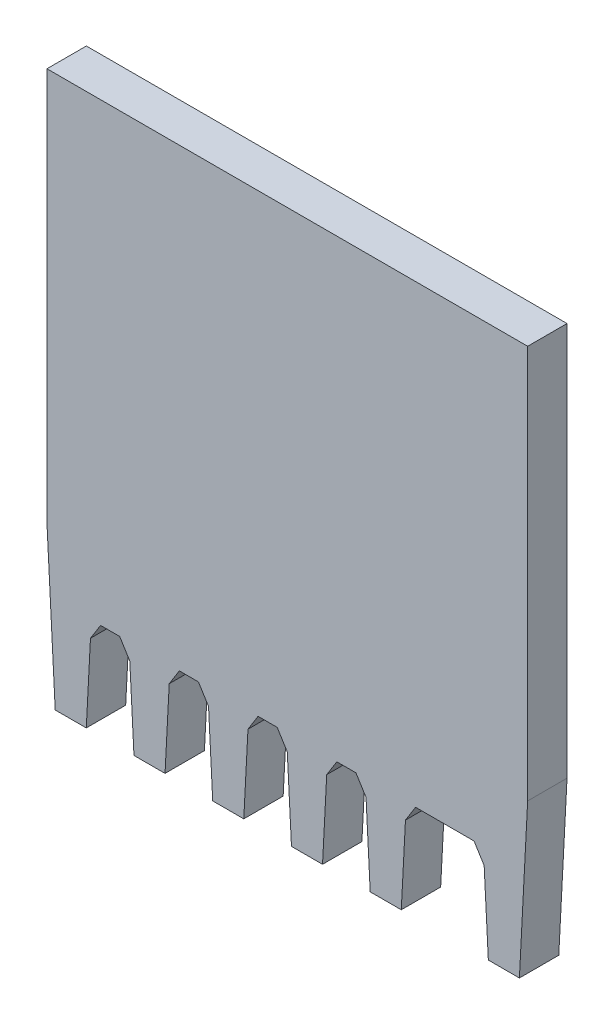
SolidWorks part; units mm, degrees
ref_plane "Front Plane" through (0, 0, 0) normal (0, 0, 1) x (1, 0, 0)
ref_plane "Top Plane" through (0, 0, 0) normal (0, 1, 0) x (1, 0, 0)
ref_plane "Right Plane" through (0, 0, 0) normal (1, 0, 0) x (0, 0, -1)
sketch "Sketch1" plane through (0, 0, 0) normal (0, 0, 1) x (1, 0, 0)
  line L0 (0, 0) -> (0, 21) construction
  line L1 (0, 21) -> (18.3124, 21) construction
  line L2 (18.3124, 21) -> (18.3124, 0) construction
  line L3 (18.3124, 0) -> (0, 0) construction
  line L4 (0, 3) -> (18.3124, 3) construction
  line L5 (0, 6) -> (18.3124, 6) construction
  line L6 (0.9062, 6) -> (0.9062, 0) construction
  line L7 (3.9062, 6) -> (3.9062, 0) construction
  line L8 (6.9062, 6) -> (6.9062, 0) construction
  line L9 (9.9062, 6) -> (9.9062, 0) construction
  line L10 (12.9062, 6) -> (12.9062, 0) construction
  line L11 (17.4062, 6) -> (17.4062, 0) construction
  line L12 (0.9062, 3) -> (3.9062, 3) construction
  line L13 (3.9062, 3) -> (6.9062, 3) construction
  line L14 (6.9062, 3) -> (9.9062, 3) construction
  line L15 (9.9062, 3) -> (12.9062, 3) construction
  line L16 (12.9062, 3) -> (17.4062, 3) construction
  line L17 (0.9062, 3) -> (0, 3) construction
  line L18 (17.4062, 3) -> (18.3124, 3) construction
  line L19 (2.4062, 3) -> (2.4062, 0) construction
  line L20 (5.4062, 3) -> (5.4062, 0) construction
  line L21 (8.4062, 3) -> (8.4062, 0) construction
  line L22 (11.4062, 3) -> (11.4062, 0) construction
  line L23 (15.1562, 3) -> (15.1562, 0) construction
  line L24 (14.4062, 3.75) -> (15.9062, 3.75) construction
  line L25 (0, 6) -> (0.3144, 0)
  line L26 (0.3144, 0) -> (1.4979, 0)
  line L27 (1.4979, 0) -> (1.6572, 3.0393)
  line L28 (3.1552, 3.0393) -> (3.3144, 0)
  line L29 (3.3144, 0) -> (4.4979, 0)
  line L30 (4.4979, 0) -> (4.6572, 3.0393)
  line L31 (6.1552, 3.0393) -> (6.3144, 0)
  line L32 (6.3144, 0) -> (7.4979, 0)
  line L33 (7.4979, 0) -> (7.6572, 3.0393)
  line L34 (9.1552, 3.0393) -> (9.3144, 0)
  line L35 (9.3144, 0) -> (10.4979, 0)
  line L36 (10.4979, 0) -> (10.6572, 3.0393)
  line L37 (12.1552, 3.0393) -> (12.3144, 0)
  line L38 (12.3144, 0) -> (13.4979, 0)
  line L39 (13.4979, 0) -> (13.6572, 3.0393)
  line L40 (16.6552, 3.0393) -> (16.8144, 0)
  line L41 (16.8144, 0) -> (17.9979, 0)
  line L42 (17.9979, 0) -> (18.3124, 6)
  line L44 (1.6572, 3.0393) -> (2.0426, 3.656)
  line L45 (0, 6) -> (0, 21)
  line L46 (0, 21) -> (18.3124, 21)
  line L47 (18.3124, 21) -> (18.3124, 6)
  line L48 (9.1562, 21) -> (9.1562, 6) construction
  line L49 (2.0426, 3.656) -> (2.7698, 3.656)
  line L50 (2.7698, 3.656) -> (3.1552, 3.0393)
  line L51 (4.6572, 3.0393) -> (5.0426, 3.656)
  line L52 (5.0426, 3.656) -> (5.7698, 3.656)
  line L53 (5.7698, 3.656) -> (6.1552, 3.0393)
  line L54 (7.6572, 3.0393) -> (8.0426, 3.656)
  line L55 (8.0426, 3.656) -> (8.7698, 3.656)
  line L56 (8.7698, 3.656) -> (9.1552, 3.0393)
  line L57 (10.6572, 3.0393) -> (11.0426, 3.656)
  line L58 (11.0426, 3.656) -> (11.7698, 3.656)
  line L59 (11.7698, 3.656) -> (12.1552, 3.0393)
  line L60 (13.6572, 3.0393) -> (14.0426, 3.656)
  line L61 (14.0426, 3.656) -> (16.2698, 3.656)
  line L62 (16.2698, 3.656) -> (16.6552, 3.0393)
  arc A0 (3.1552, 3.0393) -> (1.6572, 3.0393) centre (2.4062, 3) ccw construction
  arc A1 (6.1552, 3.0393) -> (4.6572, 3.0393) centre (5.4062, 3) ccw construction
  arc A2 (9.1552, 3.0393) -> (7.6572, 3.0393) centre (8.4062, 3) ccw construction
  arc A3 (12.1552, 3.0393) -> (10.6572, 3.0393) centre (11.4062, 3) ccw construction
  arc A4 (13.6572, 3.0393) -> (14.4062, 3.75) centre (14.4062, 3) cw construction
  arc A5 (16.6552, 3.0393) -> (15.9062, 3.75) centre (15.9062, 3) ccw construction
  dimension "D7" = 0.75
  dimension "D1" = 3
  dimension "D2" = 6
  dimension "D3" = 15
  dimension "D4" = 3
  dimension "D6" = 4.5
  dimension "D8" = 3
  dimension "D9" = 18.3124
  dimension "D10" = 21
extrude "Boss-Extrude1" add sketch "Sketch1" along normal blind 1.5
sketch "Sketch3" plane through (0, 0, 0) normal (0, 0, 1) x (1, 0, 0)
  line L0 (-0.4005, 6) -> (18.7129, 6)
  line L1 (18.7129, 3) -> (-0.4005, 3) construction
  line L2 (-0.4005, 0) -> (18.7129, 0) construction
  line L3 (-0.4005, -0.5) -> (18.7129, -0.5) construction
  line L4 (18.7129, -0.5) -> (18.7129, 6) construction
  line L5 (-0.4005, 6) -> (-0.4005, -0.5) construction
  line L6 (18.3124, 0) -> (0, 0) construction
  line L7 (0, 3) -> (18.3124, 3) construction
  line L8 (0, 6) -> (18.3124, 6) construction
  line L9 (0.3407, -0.5) -> (0, 6) construction
  line L10 (18.3124, 6) -> (17.9717, -0.5) construction
  line L11 (17.9979, 0) -> (18.3124, 6) construction
  line L12 (0, 6) -> (0.3144, 0) construction
  line L13 (5.4062, 6) -> (5.4062, -0.5) construction
  line L14 (3.9062, 6) -> (3.9062, -0.5) construction
  line L15 (5.4062, 3) -> (5.4062, 0) construction
  line L16 (3.1572, 3) -> (3.3407, -0.5) construction
  line L17 (2.7567, 3) -> (2.9401, -0.5)
  line L18 (3.1552, 3.0393) -> (3.3144, 0) construction
  line L19 (2.9401, -0.5) -> (4.8723, -0.5)
  line L20 (4.8723, -0.5) -> (5.0557, 3)
  line L21 (2.8484, 1.25) -> (3.2478, 1.2709) construction
  line L22 (5.9401, -0.5) -> (5.7567, 3)
  line L26 (7.8723, -0.5) -> (5.9401, -0.5)
  line L27 (8.0557, 3) -> (7.8723, -0.5)
  line L30 (2.4062, -0.5) -> (2.4062, 6) construction
  line L31 (2.4062, 3) -> (2.4062, 0) construction
  line L32 (8.4062, 6) -> (8.4062, -0.5) construction
  line L34 (11.4062, -0.5) -> (11.4062, 6) construction
  line L35 (15.1562, -0.5) -> (15.1562, 6) construction
  line L36 (8.4062, 3) -> (8.4062, 0) construction
  line L37 (11.4062, 3) -> (11.4062, 0) construction
  line L38 (15.1562, 3) -> (15.1562, 0) construction
  line L39 (10.8723, -0.5) -> (11.0557, 3)
  line L40 (8.9401, -0.5) -> (10.8723, -0.5)
  line L41 (8.7567, 3) -> (8.9401, -0.5)
  line L42 (11.9401, -0.5) -> (11.7567, 3)
  line L43 (13.8723, -0.5) -> (11.9401, -0.5)
  line L44 (14.0557, 3) -> (13.8723, -0.5)
  line L45 (16.4401, -0.5) -> (18.3723, -0.5)
  line L46 (16.2567, 3) -> (16.4401, -0.5)
  line L47 (18.3723, -0.5) -> (18.7129, 6)
  line L48 (1.8723, -0.5) -> (-0.0599, -0.5)
  line L49 (2.0557, 3) -> (1.8723, -0.5)
  line L50 (-0.0599, -0.5) -> (-0.4005, 6)
  line L51 (16.2567, 3) -> (14.0557, 3)
  line L52 (11.7567, 3) -> (11.0557, 3)
  line L53 (8.7567, 3) -> (8.0557, 3)
  line L54 (5.7567, 3) -> (5.0557, 3)
  line L55 (2.7567, 3) -> (2.0557, 3)
  dimension "D1" = 0.5
  dimension "D2" = 0.4
ref_plane "Plane1" through (3.9062, 0, 0) normal (1, 0, 0) x (0, 0, -1)
sketch "Sketch4" plane through (3.9062, 0, 0) normal (1, 0, 0) x (0, 0, -1)
  line L0 (0, 6) -> (0, -0.5) construction
  line L1 (0.6, 6) -> (-2.1, 6) construction
  line L2 (0.6, 6) -> (0.6, -0.5) construction
  line L3 (0.6, -0.5) -> (-2.1, -0.5) construction
  line L4 (-2.1, 6) -> (-2.1, -0.5) construction
  line L5 (-0.75, -0.5) -> (-0.75, 6) construction
  line L6 (-1.5, 6) -> (-1.5, -0.5) construction
  line L7 (0.6, 2.4005) -> (-2.1, 2.4005) construction
  line L8 (0.3, 6) -> (0.3, -0.5) construction
  line L9 (0.6, 2.4005) -> (3.846, 6) construction
  line L10 (2.2302, 6) -> (0.6, 4.1923) construction
  line L11 (0.6, 4.1923) -> (1.7139, 3.1878) construction
  line L12 (1.7139, 3.1878) -> (4.25, 6)
  line L13 (4.25, 6) -> (0.6, 6) construction
  line L14 (0.3, 1) -> (-1.8, 1) construction
  line L15 (-2.1, 0) -> (0.6, 0) construction
  line L16 (1.7139, 3.1878) -> (1.4912, 3.3887)
  line L17 (1.4912, 3.3887) -> (0.6, 2.4005)
  line L18 (-3.2139, 3.1878) -> (-5.75, 6)
  line L19 (-3.2139, 3.1878) -> (-2.9912, 3.3887)
  line L20 (-2.9912, 3.3887) -> (-2.1, 2.4005)
  line L21 (-2.1, 6) -> (-5.75, 6) construction
  line L22 (0.6, 3.0724) -> (3.2401, 6) construction
  arc A0 (0.4965, 2.2224) -> (0.6, -0.5) centre (4.2, 1) ccw
  arc A1 (0.6, 2.4005) -> (0.4965, 2.2224) centre (0.9713, 2.0656) ccw
  arc A2 (-2.1, 2.4005) -> (-1.9965, 2.2224) centre (-2.4713, 2.0656) cw
  arc A3 (-1.9965, 2.2224) -> (-2.1, -0.5) centre (-5.7, 1) cw
  dimension "D6" = 0.5
  dimension "D1" = 0.6
  dimension "D2" = 0.3
  dimension "D3" = 1.5
  dimension "D4" = 1
  dimension "D5" = 0.3
  dimension "D7" = 10
sketch "Sketch5" plane through (0, 0, 0) normal (1, 0, 0) x (0, 0, -1)
  line L0 (2.2302, 6) -> (0.6, 4.1923) construction
  line L1 (0.6, 4.1923) -> (1.7139, 3.1878) construction
  line L2 (1.7139, 3.1878) -> (4.25, 6) construction
  line L3 (2.2302, 6) -> (0.6, 4.1923) construction
  line L4 (0.6, 4.1923) -> (1.7139, 3.1878) construction
  line L5 (1.7139, 3.1878) -> (4.25, 6) construction
ref_plane "Plane2" through (0, 2.6105, -2.3541) normal (0, 0.7426, -0.6697) x (1, 0, 0)
sketch "Sketch6" plane through (0, 2.6105, -2.3541) normal (0, 0.7426, -0.6697) x (1, 0, 0)
  line L1 (3.9062, -2.362) -> (3.9062, -0.862) construction
  line L2 (3.9062, -2.362) -> (3.9062, -5.0612) construction
  line L3 (4.6562, -5.0612) -> (3.1562, -5.0612)
  line L4 (4.6562, -1.612) -> (3.1562, -1.612) construction
  line L5 (3.1562, -1.612) -> (3.1562, -5.0612)
  line L6 (4.6562, -1.612) -> (4.6562, -5.0612)
  line L10 (2.4062, -5.0612) -> (15.1562, -5.0612) construction
  line L11 (15.1562, -5.0612) -> (15.1562, -0.862) construction
  line L12 (15.1562, -0.862) -> (2.4062, -0.862) construction
  line L13 (2.4062, -0.862) -> (2.4062, -5.0612) construction
  line L14 (15.1562, 0.3349) -> (15.1562, -4.0182) construction
  line L15 (2.4062, 0.3349) -> (2.4062, -4.0182) construction
  line L16 (11.4062, -5.0612) -> (11.4062, -0.862) construction
  line L17 (8.4062, -5.0612) -> (8.4062, -0.862) construction
  line L18 (5.4062, -5.0612) -> (5.4062, -0.862) construction
  line L19 (5.4062, -4.0182) -> (5.4062, 0.3349) construction
  line L20 (8.4062, -4.0182) -> (8.4062, 0.3349) construction
  line L21 (11.4062, 0.3349) -> (11.4062, -4.0182) construction
  line L22 (0.1562, -1.612) -> (0.1562, -5.0612)
  line L23 (0.1562, -5.0612) -> (1.6562, -5.0612)
  line L24 (1.6562, -1.612) -> (1.6562, -5.0612)
  line L25 (7.6562, -1.612) -> (7.6562, -5.0612)
  line L26 (6.1562, -5.0612) -> (7.6562, -5.0612)
  line L27 (6.1562, -1.612) -> (6.1562, -5.0612)
  line L28 (10.6562, -1.612) -> (10.6562, -5.0612)
  line L29 (10.6562, -5.0612) -> (9.1562, -5.0612)
  line L30 (9.1562, -1.612) -> (9.1562, -5.0612)
  line L31 (13.6562, -1.612) -> (13.6562, -5.0612)
  line L32 (12.1562, -5.0612) -> (13.6562, -5.0612)
  line L33 (12.1562, -1.612) -> (12.1562, -5.0612)
  line L34 (18.1562, -1.612) -> (18.1562, -5.0612)
  line L35 (18.1562, -5.0612) -> (16.6562, -5.0612)
  line L36 (16.6562, -1.612) -> (16.6562, -5.0612)
  circle A0 centre (3.9062, -1.612) radius 0.75 construction
  arc A1 (4.6562, -1.612) -> (3.1562, -1.612) centre (3.9062, -1.612) ccw
  arc A2 (0.1562, -1.612) -> (1.6562, -1.612) centre (0.9062, -1.612) cw
  arc A3 (6.1562, -1.612) -> (7.6562, -1.612) centre (6.9062, -1.612) cw
  arc A4 (10.6562, -1.612) -> (9.1562, -1.612) centre (9.9062, -1.612) ccw
  arc A5 (12.1562, -1.612) -> (13.6562, -1.612) centre (12.9062, -1.612) cw
  arc A6 (18.1562, -1.612) -> (16.6562, -1.612) centre (17.4062, -1.612) ccw
ref_plane "Plane3" through (0, 1.6223, -1.463) normal (0, 0.7426, -0.6697) x (1, 0, 0)
sketch "Sketch7" plane through (0, 1.6223, -1.463) normal (0, 0.7426, -0.6697) x (1, 0, 0)
  line L0 (3.1562, -1.612) -> (3.1562, -5.0612) construction
  line L1 (4.6562, -5.0612) -> (3.1562, -5.0612) construction
  line L2 (4.6562, -1.612) -> (4.6562, -5.0612) construction
  line L3 (3.1562, -1.612) -> (3.1562, -5.0612) construction
  line L4 (4.6562, -5.0612) -> (3.1562, -5.0612) construction
  line L5 (4.6562, -1.612) -> (4.6562, -5.0612) construction
  line L6 (3.9062, -0.862) -> (3.9062, -5.0612) construction
  line L7 (4.6562, -1.612) -> (3.1562, -1.612) construction
  line L8 (4.6562, -2.362) -> (3.1562, -2.362) construction
  line L9 (3.4562, -1.612) -> (3.4562, -2.362)
  line L10 (3.4562, -2.362) -> (4.3562, -2.362)
  line L11 (4.3562, -2.362) -> (4.3562, -1.612)
  line L12 (2.4062, -0.862) -> (2.4062, -5.0612) construction
  line L13 (2.4062, -5.0612) -> (15.1562, -5.0612) construction
  line L14 (15.1562, -0.862) -> (2.4062, -0.862) construction
  line L15 (5.4062, -5.0612) -> (5.4062, -0.862) construction
  line L16 (8.4062, -5.0612) -> (8.4062, -0.862) construction
  line L17 (11.4062, -5.0612) -> (11.4062, -0.862) construction
  line L18 (15.1562, -5.0612) -> (15.1562, -0.862) construction
  line L19 (2.4062, -0.862) -> (2.4062, -5.0612) construction
  line L20 (2.4062, -5.0612) -> (15.1562, -5.0612) construction
  line L21 (15.1562, -0.862) -> (2.4062, -0.862) construction
  line L22 (5.4062, -5.0612) -> (5.4062, -0.862) construction
  line L23 (8.4062, -5.0612) -> (8.4062, -0.862) construction
  line L24 (11.4062, -5.0612) -> (11.4062, -0.862) construction
  line L25 (15.1562, -5.0612) -> (15.1562, -0.862) construction
  line L26 (0.4562, -2.362) -> (0.4562, -1.612)
  line L27 (1.3562, -2.362) -> (0.4562, -2.362)
  line L28 (1.3562, -1.612) -> (1.3562, -2.362)
  line L29 (7.3562, -2.362) -> (6.4562, -2.362)
  line L30 (7.3562, -1.612) -> (7.3562, -2.362)
  line L31 (6.4562, -2.362) -> (6.4562, -1.612)
  line L32 (9.4562, -1.612) -> (9.4562, -2.362)
  line L33 (10.3562, -2.362) -> (10.3562, -1.612)
  line L34 (9.4562, -2.362) -> (10.3562, -2.362)
  line L35 (13.3562, -1.612) -> (13.3562, -2.362)
  line L36 (12.4562, -2.362) -> (12.4562, -1.612)
  line L37 (13.3562, -2.362) -> (12.4562, -2.362)
  line L38 (16.9562, -1.612) -> (16.9562, -2.362)
  line L39 (17.8562, -2.362) -> (17.8562, -1.612)
  line L40 (16.9562, -2.362) -> (17.8562, -2.362)
  arc A0 (4.6562, -1.612) -> (3.1562, -1.612) centre (3.9062, -1.612) ccw construction
  arc A1 (4.6562, -1.612) -> (3.1562, -1.612) centre (3.9062, -1.612) ccw construction
  circle A2 centre (3.9062, -1.612) radius 0.45 construction
  arc A3 (4.3562, -1.612) -> (3.4562, -1.612) centre (3.9062, -1.612) ccw
  arc A4 (0.4562, -1.612) -> (1.3562, -1.612) centre (0.9062, -1.612) cw
  arc A5 (6.4562, -1.612) -> (7.3562, -1.612) centre (6.9062, -1.612) cw
  arc A6 (10.3562, -1.612) -> (9.4562, -1.612) centre (9.9062, -1.612) ccw
  arc A7 (12.4562, -1.612) -> (13.3562, -1.612) centre (12.9062, -1.612) cw
  arc A8 (17.8562, -1.612) -> (16.9562, -1.612) centre (17.4062, -1.612) ccw
ref_plane "bisect" through (0, 0, 0.75) normal (0, 0, 1) x (1, 0, 0)
ref_plane "insert_surface" through (0, 6, 0) normal (0, 1, 0) x (1, 0, 0)
sketch "Sketch8" plane through (0, 6, 0) normal (0, 1, 0) x (1, 0, 0)
  line L0 (18.7129, -0.75) -> (-0.4005, -0.75) construction
  line L1 (-0.4005, 0.6) -> (18.7129, 0.6)
  line L2 (-0.4005, 0.6) -> (-0.4005, -2.1)
  line L3 (-0.4005, -2.1) -> (18.7129, -2.1)
  line L4 (18.7129, 0.6) -> (18.7129, -2.1)
  line L5 (9.1562, 0.6) -> (9.1562, -2.1) construction
  line L6 (0, 0) -> (18.3124, 0) construction
  line L7 (0, 0) -> (0, -1.5) construction
  line L8 (0, -1.5) -> (18.3124, -1.5) construction
  line L9 (18.3124, 0) -> (18.3124, -1.5) construction
  line L10 (18.7129, 0.3) -> (-0.4005, 0.3) construction
  line L11 (18.7129, -1.8) -> (-0.4005, -1.8) construction
sketch "Sketch9" plane through (0, 0, 0) normal (0, 0, 1) x (1, 0, 0)
  line L0 (18.3723, -0.5) -> (18.7129, 6) construction
  line L1 (-0.4005, 6) -> (18.7129, 6) construction
  line L2 (-0.0599, -0.5) -> (-0.4005, 6) construction
  line L3 (1.8723, -0.5) -> (-0.0599, -0.5) construction
  line L4 (2.0557, 3) -> (1.8723, -0.5) construction
  line L5 (2.7567, 3) -> (2.0557, 3) construction
  line L6 (2.7567, 3) -> (2.9401, -0.5) construction
  line L7 (2.9401, -0.5) -> (4.8723, -0.5) construction
  line L8 (4.8723, -0.5) -> (5.0557, 3) construction
  line L9 (5.7567, 3) -> (5.0557, 3) construction
  line L10 (5.9401, -0.5) -> (5.7567, 3) construction
  line L11 (7.8723, -0.5) -> (5.9401, -0.5) construction
  line L12 (8.0557, 3) -> (7.8723, -0.5) construction
  line L13 (8.7567, 3) -> (8.0557, 3) construction
  line L14 (8.7567, 3) -> (8.9401, -0.5) construction
  line L15 (8.9401, -0.5) -> (10.8723, -0.5) construction
  line L16 (10.8723, -0.5) -> (11.0557, 3) construction
  line L17 (11.7567, 3) -> (11.0557, 3) construction
  line L18 (11.9401, -0.5) -> (11.7567, 3) construction
  line L19 (13.8723, -0.5) -> (11.9401, -0.5) construction
  line L20 (14.0557, 3) -> (13.8723, -0.5) construction
  line L21 (16.2567, 3) -> (14.0557, 3) construction
  line L22 (16.2567, 3) -> (16.4401, -0.5) construction
  line L23 (16.4401, -0.5) -> (18.3723, -0.5) construction
  line L24 (18.3723, -0.5) -> (18.7129, 6)
  line L25 (-0.4005, 6) -> (18.7129, 6) construction
  line L26 (-0.0599, -0.5) -> (-0.4005, 6)
  line L27 (1.8723, -0.5) -> (-0.0599, -0.5)
  line L28 (2.0557, 3) -> (1.8723, -0.5)
  line L29 (2.7567, 3) -> (2.0557, 3) construction
  line L30 (2.7567, 3) -> (2.9401, -0.5)
  line L31 (2.9401, -0.5) -> (4.8723, -0.5)
  line L32 (4.8723, -0.5) -> (5.0557, 3)
  line L33 (5.7567, 3) -> (5.0557, 3) construction
  line L34 (5.9401, -0.5) -> (5.7567, 3)
  line L35 (7.8723, -0.5) -> (5.9401, -0.5)
  line L36 (8.0557, 3) -> (7.8723, -0.5)
  line L37 (8.7567, 3) -> (8.0557, 3) construction
  line L38 (8.7567, 3) -> (8.9401, -0.5)
  line L39 (8.9401, -0.5) -> (10.8723, -0.5)
  line L40 (10.8723, -0.5) -> (11.0557, 3)
  line L41 (11.7567, 3) -> (11.0557, 3) construction
  line L42 (11.9401, -0.5) -> (11.7567, 3)
  line L43 (13.8723, -0.5) -> (11.9401, -0.5)
  line L44 (14.0557, 3) -> (13.8723, -0.5)
  line L45 (16.2567, 3) -> (14.0557, 3) construction
  line L46 (16.2567, 3) -> (16.4401, -0.5)
  line L47 (16.4401, -0.5) -> (18.3723, -0.5)
  line L48 (16.2567, 3) -> (16.2567, 6)
  line L49 (14.0557, 3) -> (14.0557, 6)
  line L50 (11.7567, 3) -> (11.7567, 6)
  line L51 (18.7129, 6) -> (-0.4005, 6) construction
  line L52 (11.0557, 3) -> (11.0557, 6)
  line L53 (-0.4005, 6) -> (18.7129, 6) construction
  line L54 (8.7567, 3) -> (8.7567, 6)
  line L55 (8.0557, 3) -> (8.0557, 6)
  line L58 (5.7567, 3) -> (5.7567, 6)
  line L60 (5.0557, 3) -> (5.0557, 6)
  line L62 (15.1562, -0.5) -> (15.1562, 6) construction
  line L63 (15.1562, -0.5) -> (15.1562, 6) construction
  line L64 (2.7567, 3) -> (2.7567, 6)
  line L65 (2.0557, 3) -> (2.0557, 6)
  line L67 (18.7129, 6) -> (16.2567, 6)
  line L68 (14.0557, 6) -> (11.7567, 6)
  line L69 (11.0557, 6) -> (8.7567, 6)
  line L70 (8.0557, 6) -> (5.7567, 6)
  line L71 (5.0557, 6) -> (2.7567, 6)
  line L72 (2.0557, 6) -> (-0.4005, 6)
